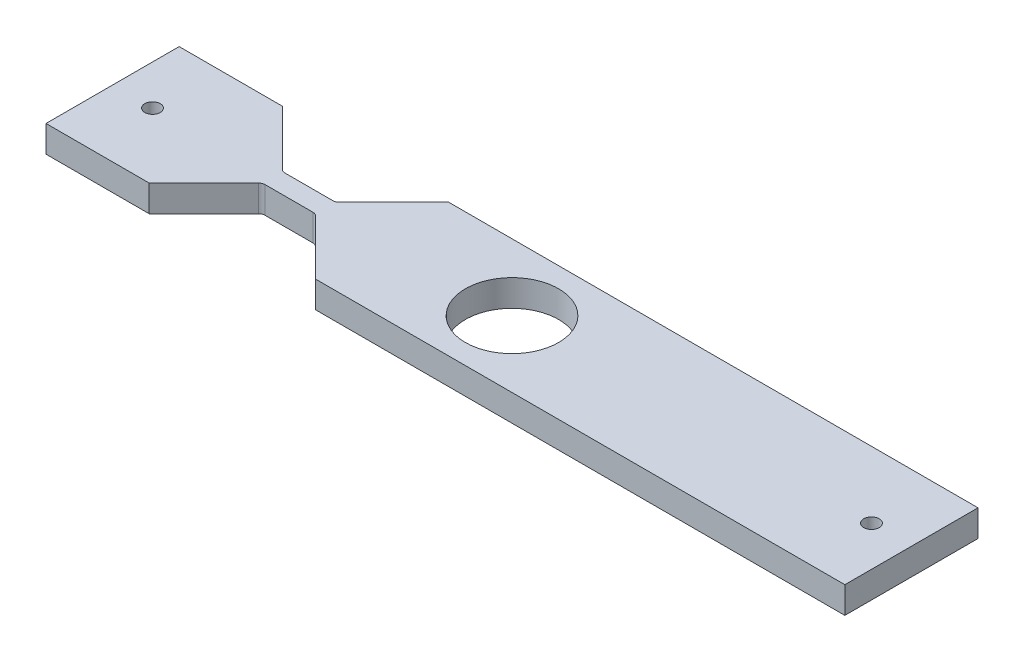
SolidWorks part; units mm, degrees
material "6061-T6 (SS)"
ref_plane "Front Plane" through (0, 0, 0) normal (0, 0, 1) x (1, 0, 0)
ref_plane "Top Plane" through (0, 0, 0) normal (0, 1, 0) x (1, 0, 0)
ref_plane "Right Plane" through (0, 0, 0) normal (1, 0, 0) x (0, 0, -1)
sketch "Sketch1" plane through (0, 0, 0) normal (0, 1, 0) x (1, 0, 0)
  line L1 (-190.5, 31.75) -> (190.5, 31.75)
  line L2 (-190.5, 31.75) -> (-190.5, -31.75)
  line L3 (-190.5, -31.75) -> (190.5, -31.75)
  line L4 (190.5, 31.75) -> (190.5, -31.75)
  line L5 (-190.5, 31.75) -> (190.5, -31.75) construction
  line L6 (-190.5, -31.75) -> (190.5, 31.75) construction
  point P0 (0, 0)
  dimension "D1" = 381
  dimension "D2" = 63.5
extrude "Boss-Extrude1" add sketch "Sketch1" along normal blind 12.7
sketch "Sketch2" plane through (0, 12.7, 0) normal (0, 1, 0) x (1, 0, 0)
  circle A0 centre (0, 0) radius 22.225
  dimension "D1" = 44.45
extrude "Cut-Extrude1" cut sketch "Sketch2" against normal through all
sketch "Sketch3" plane through (0, 12.7, 0) normal (0, 1, 0) x (1, 0, 0)
  line L0 (190.5, 31.75) -> (-190.5, 31.75) construction
  line L1 (-141.2875, 31.75) -> (-61.9125, 31.75)
  line L2 (-141.2875, 31.75) -> (-114.3, 4.7625)
  line L3 (-114.3, 4.7625) -> (-88.9, 4.7625)
  line L4 (-61.9125, 31.75) -> (-88.9, 4.7625)
  line L5 (-190.5, -31.75) -> (190.5, -31.75) construction
  line L6 (-141.2875, -31.75) -> (-61.9125, -31.75)
  line L7 (-141.2875, -31.75) -> (-114.3, -4.7625)
  line L8 (-114.3, -4.7625) -> (-88.9, -4.7625)
  line L9 (-61.9125, -31.75) -> (-88.9, -4.7625)
  line L11 (-190.5, 31.75) -> (-190.5, -31.75) construction
  point P12 (-82.15, 31.75)
  point P13 (-84.4382, 31.75)
  point P16 (-82.5591, -31.75)
  point P17 (-82.5591, 31.75)
  point P18 (0, 0)
  point P19 (-125.8378, 31.75)
  point P20 (0, 0)
  point P21 (-126.7134, -31.75)
  point P22 (0, 0)
  point P23 (-67.8915, 31.75)
  point P24 (-66.3367, 31.75)
  dimension "D1" = 9.525
  dimension "D2" = 25.4
  dimension "D3" = 76.2
  dimension "D4" = 45
extrude "Cut-Extrude2" cut sketch "Sketch3" against normal through all
fillet "Fillet1" radius 3.175 4 edges at (-114.3, 6.35, -4.7625) (-88.9, 6.35, -4.7625) (-88.9, 6.35, 4.7625) (-114.3, 6.35, 4.7625)
sketch "Sketch4" plane through (0, 12.7, 0) normal (0, 1, 0) x (1, 0, 0)
  line L0 (-171.45, 0) -> (-190.5, 0) construction
  line L1 (-190.5, 31.75) -> (-190.5, -31.75) construction
  line L2 (171.45, 0) -> (190.5, 0) construction
  line L3 (190.5, -31.75) -> (190.5, 31.75) construction
  circle A0 centre (-171.45, 0) radius 3.683
  circle A1 centre (171.45, 0) radius 3.683
  point P11 (0, 0)
  dimension "D1" = 7.366
  dimension "D2" = 342.9
extrude "Cut-Extrude3" cut sketch "Sketch4" against normal through all
